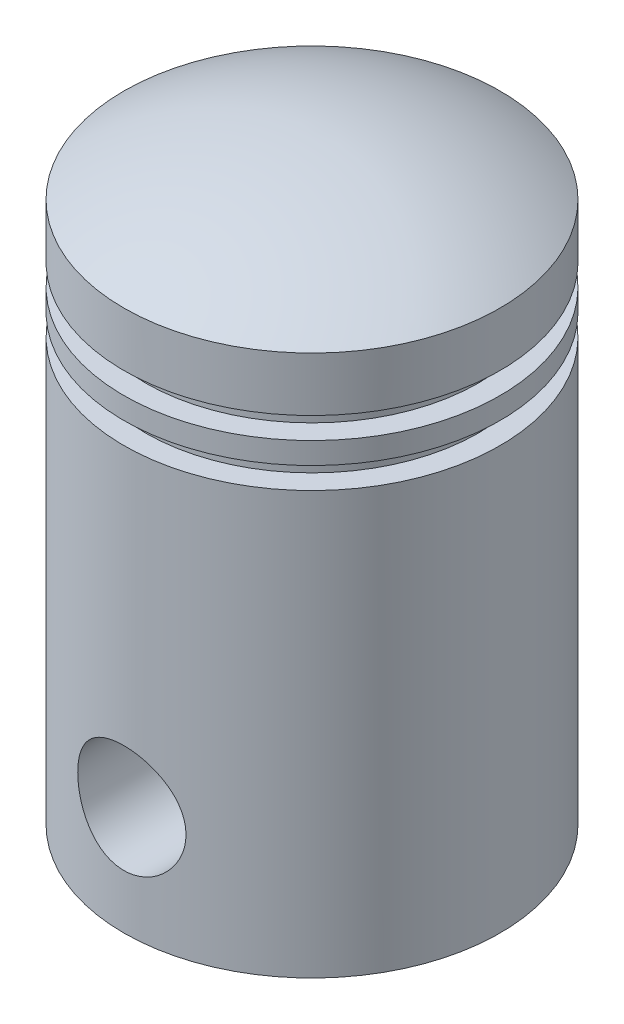
SolidWorks part; units mm, degrees
material "4032-T6"
ref_plane "Front Plane" through (0, 0, 0) normal (0, 0, 1) x (1, 0, 0)
ref_plane "Top Plane" through (0, 0, 0) normal (0, 1, 0) x (1, 0, 0)
ref_plane "Right Plane" through (0, 0, 0) normal (1, 0, 0) x (0, 0, -1)
sketch "Sketch3" plane through (0, 0, 0) normal (0, 1, 0) x (1, 0, 0)
  circle A0 centre (0, 0) radius 17.375
extrude "Boss-Extrude1" add sketch "Sketch3" along normal blind 30
sketch "Sketch4" plane through (0, 30, 0) normal (0, 1, 0) x (1, 0, 0)
  circle A0 centre (0, 0) radius 17.375
extrude "Boss-Extrude2" add sketch "Sketch4" along normal blind 20
sketch "Sketch5" plane through (0, 0, 0) normal (0, 0, 1) x (1, 0, 0)
  line L0 (0, 0) -> (0, 10)
  circle A1 centre (0, 10) radius 5
extrude "Cut-Extrude1" cut sketch "Sketch5" against normal blind 42 and the other way blind 61 contours A1
sketch "Sketch7" plane through (0, 0, 0) normal (0, -1, 0) x (1, 0, 0)
  line L0 (0, 17.375) -> (0, -17.375)
  line L1 (0, 0) -> (0, 5.25)
  line L2 (0, 0) -> (0, -5.25)
  line L3 (0, -5.25) -> (12.375, -5.25)
  line L4 (0, -5.25) -> (-12.375, -5.25)
  line L5 (0, 5.25) -> (12.375, 5.25)
  line L6 (0, 5.25) -> (-12.375, 5.25)
  line L7 (-12.375, 5.25) -> (-12.375, -5.25)
  line L8 (12.375, 5.25) -> (12.375, -5.25)
  circle A0 centre (0, 0) radius 17.375 construction
extrude "Cut-Extrude3" cut sketch "Sketch7" against normal blind 15 contours L6 L7 L4 L0 | L8 L5 L0 L3 region at (6.1875, 0, 0) region at (-6.1875, 0, 0)
sketch "Sketch13" plane through (0, 15, 0) normal (0, -1, 0) x (1, 0, 0)
  line L1 (-12.375, 5.25) -> (12.375, 5.25)
  line L2 (-12.375, 5.25) -> (-12.375, -5.25)
  line L3 (-12.375, -5.25) -> (12.375, -5.25)
  line L4 (12.375, 5.25) -> (12.375, -5.25)
extrude "Cut-Extrude4" cut sketch "Sketch13" against normal blind 9
dome "Dome1" faces to dome 1 distance 5 reverse direction no elliptical dome no face at (0, 50, 17.375) parameters "D1"=5
sketch "Sketch15" plane through (0, 0, 0) normal (0, 0, 1) x (1, 0, 0)
  line L0 (0, 55) -> (0, 0)
  line L1 (-17.375, 50) -> (-17.375, 0) construction
  line L2 (-17.375, 45) -> (-15.375, 45)
  line L3 (-15.375, 45) -> (-15.375, 43)
  line L4 (-15.375, 43) -> (-17.375, 43)
  line L6 (-17.375, 41) -> (-15.375, 41)
  line L7 (-15.375, 41) -> (-15.375, 39)
  line L8 (-15.375, 39) -> (-17.375, 39)
  line L9 (-17.375, 39) -> (-17.375, 41)
  line L10 (-17.375, 45) -> (-17.375, 43)
  line L11 (-17.375, 45) -> (-17.375, 43)
  line L12 (-17.375, 41) -> (-17.375, 39)
  arc A0 (17.375, 50) -> (-17.375, 50) centre (0, 22.3109) ccw construction
sketch "Sketch16" plane through (0, 0, 0) normal (0, 0, 1) x (1, 0, 0)
  line L1 (-17.375, 45) -> (-15.375, 45)
  line L2 (-17.375, 45) -> (-17.375, 43)
  line L3 (-17.375, 43) -> (-15.375, 43)
  line L4 (-15.375, 45) -> (-15.375, 43)
  line L5 (-17.375, 41) -> (-15.375, 41)
  line L6 (-17.375, 41) -> (-17.375, 39)
  line L7 (-17.375, 39) -> (-15.375, 39)
  line L8 (-15.375, 41) -> (-15.375, 39)
revolve "Cut-Revolve2" cut sketch "Sketch16" angle 360 about L0 region at (-16.375, 44, 0)
